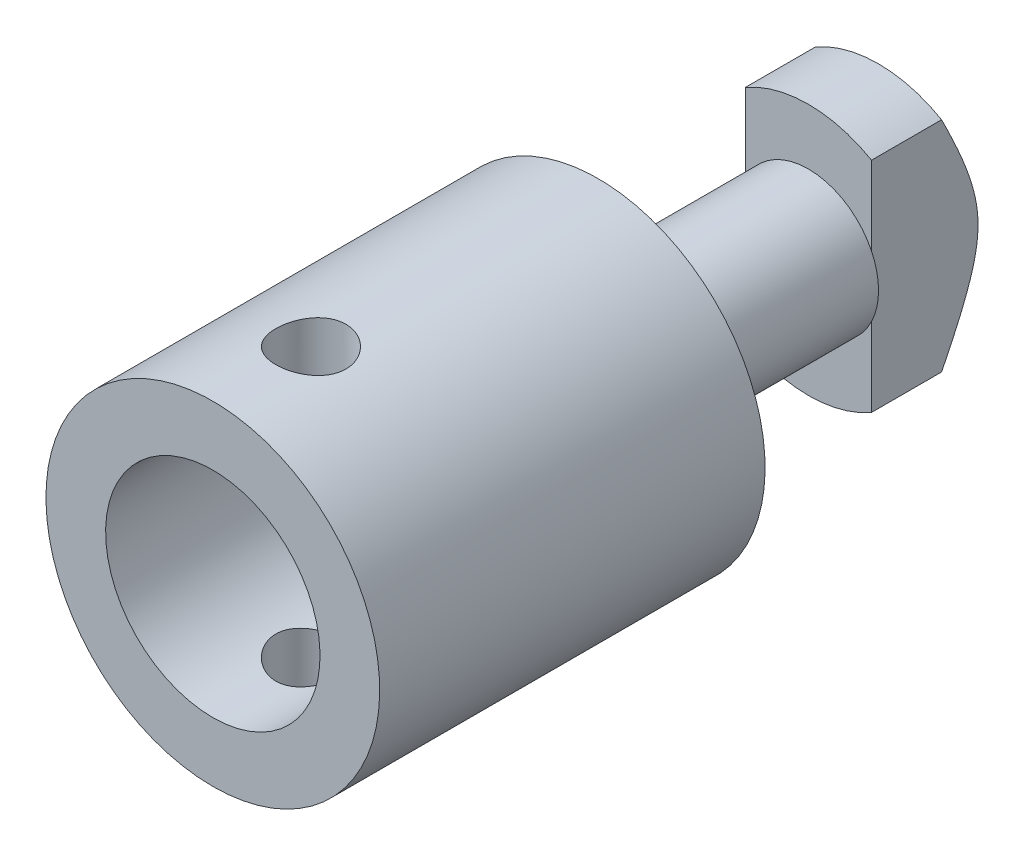
SolidWorks part; units mm, degrees
material "AISI Type 316L stainless steel"
ref_plane "Front" through (0, 0, 0) normal (0, 0, 1) x (1, 0, 0)
ref_plane "Top" through (0, 0, 0) normal (0, 1, 0) x (1, 0, 0)
ref_plane "Right" through (0, 0, 0) normal (1, 0, 0) x (0, 0, -1)
ref_axis "X" through (-80.9, 0, 0) along (1, 0, 0)
ref_axis "Y" through (0, -50, 0) along (0, 1, 0)
ref_axis "Z" through (0, 0, -80.9) along (0, 0, 1)
sketch "Sketch1" plane through (0, 0, 0) normal (1, 0, 0) x (0, 0, -1)
  line L0 (-2.9655, 0) -> (2.9655, 0) construction
  line L1 (0, 2.3813) -> (5.5, 2.3813)
  line L2 (5.5, 2.3813) -> (5.5, 1)
  line L3 (5.5, 1) -> (8.5, 1)
  line L4 (8.5, 1) -> (8.5, 1.8)
  line L5 (8.5, 1.8) -> (9.5, 1.8)
  line L8 (9.5, 1.8) -> (10.5392, 0)
  line L10 (0, 1.53) -> (0, 2.3813)
  line L11 (0, 1.53) -> (4, 1.53)
  line L12 (4, 1.53) -> (4, 0)
  line L13 (4, 0) -> (10.5392, 0)
  dimension "D1" = 3.06
  dimension "D2" = 4.7625
  dimension "D3" = 4
  dimension "D4" = 1.5
  dimension "D5" = 30
  dimension "D6" = 2
  dimension "D7" = 1
  dimension "D8" = 0.8
  dimension "D9" = 3
revolve "Revolve1" add sketch "Sketch1" angle 360 about L0
sketch "Sketch2" plane through (0, 0, 0) normal (0, 0, 1) x (1, 0, 0)
  line L0 (0.9, 5) -> (0.9, -5)
  line L1 (0.9, -5) -> (5.9, -5)
  line L2 (5.9, -5) -> (5.9, 5)
  line L3 (5.9, 5) -> (0.9, 5)
  line L4 (-5.9, 5) -> (-5.9, -5)
  line L5 (-5.9, -5) -> (-0.9, -5)
  line L6 (-0.9, -5) -> (-0.9, 5)
  line L7 (-0.9, 5) -> (-5.9, 5)
  line L8 (0, 0) -> (0.9, 0) construction
  line L9 (0, 0) -> (-0.9, 0) construction
  dimension "D1" = 1.8
  dimension "D2" = 10
  dimension "D3" = 5
extrude "Cut-Extrude1" cut sketch "Sketch2" against normal through all from surface starting at face at (0, -1, -8.5)
sketch "Sketch3" plane through (0, 0, 0) normal (0, 1, 0) x (1, 0, 0)
  line L0 (0, 1.4) -> (0, 0) construction
  circle A0 centre (0, 1.4) radius 0.5
  dimension "D1" = 1
  dimension "D2" = 1.4
extrude "Cut-Extrude2" cut sketch "Sketch3" against normal through all both and the other way through all
